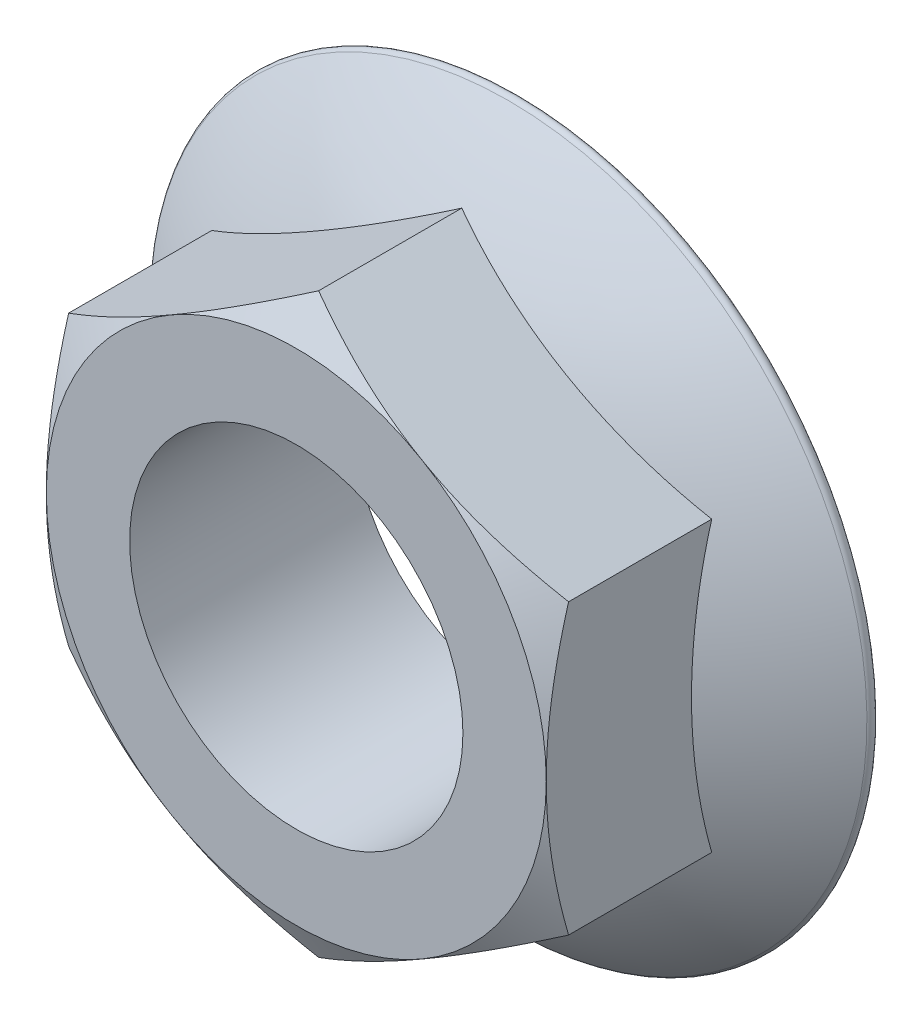
SolidWorks part; units mm, degrees
ref_plane "Front Plane" through (0, 0, 0) normal (0, 0, 1) x (1, 0, 0)
ref_plane "Top Plane" through (0, 0, 0) normal (0, 1, 0) x (1, 0, 0)
ref_plane "Right Plane" through (0, 0, 0) normal (1, 0, 0) x (0, 0, -1)
sketch "Sketch1" plane through (0, 0, 0) normal (0, 0, 1) x (1, 0, 0)
  line L1 (22.5, -12.9904) -> (22.5, 12.9904)
  line L2 (22.5, 12.9904) -> (0, 25.9808)
  line L3 (0, 25.9808) -> (-22.5, 12.9904)
  line L4 (-22.5, 12.9904) -> (-22.5, -12.9904)
  line L5 (-22.5, -12.9904) -> (0, -25.9808)
  line L6 (0, -25.9808) -> (22.5, -12.9904)
  circle A0 centre (0, 0) radius 22.5 construction
  dimension "D1" = 45
extrude "Boss-Extrude1" add sketch "Sketch1" along normal blind 20
sketch "Sketch2" plane through (0, 0, 0) normal (1, 0, 0) x (0, 0, -1)
  line L0 (0, 0) -> (-12, 0)
  line L1 (0, -31.95) -> (0, 0)
  arc A0 (-12, 0) -> (-0.894, -32.2578) centre (40.4001, 0) ccw
  arc A1 (-0.894, -32.2578) -> (0, -31.95) centre (-0.5, -31.95) ccw
  dimension "D2" = 0.5
  dimension "D1" = 12
  dimension "D3" = 31.95
revolve "Revolve1" add sketch "Sketch2" angle 360 about L0
sketch "Sketch3" plane through (0, 0, 20) normal (0, 0, 1) x (1, 0, 0)
  circle A0 centre (0, 0) radius 22.5
extrude "Cut-Extrude1" cut sketch "Sketch3" against normal blind 20 draft 60 flip side to cut
sketch "Sketch4" plane through (0, 0, 20) normal (0, 0, 1) x (1, 0, 0)
  circle A0 centre (0, 0) radius 15
  dimension "D1" = 30
extrude "Cut-Extrude2" cut sketch "Sketch4" against normal through all
cosmetic thread "Cosmetic Thread1" parameters "D2"=31.75
